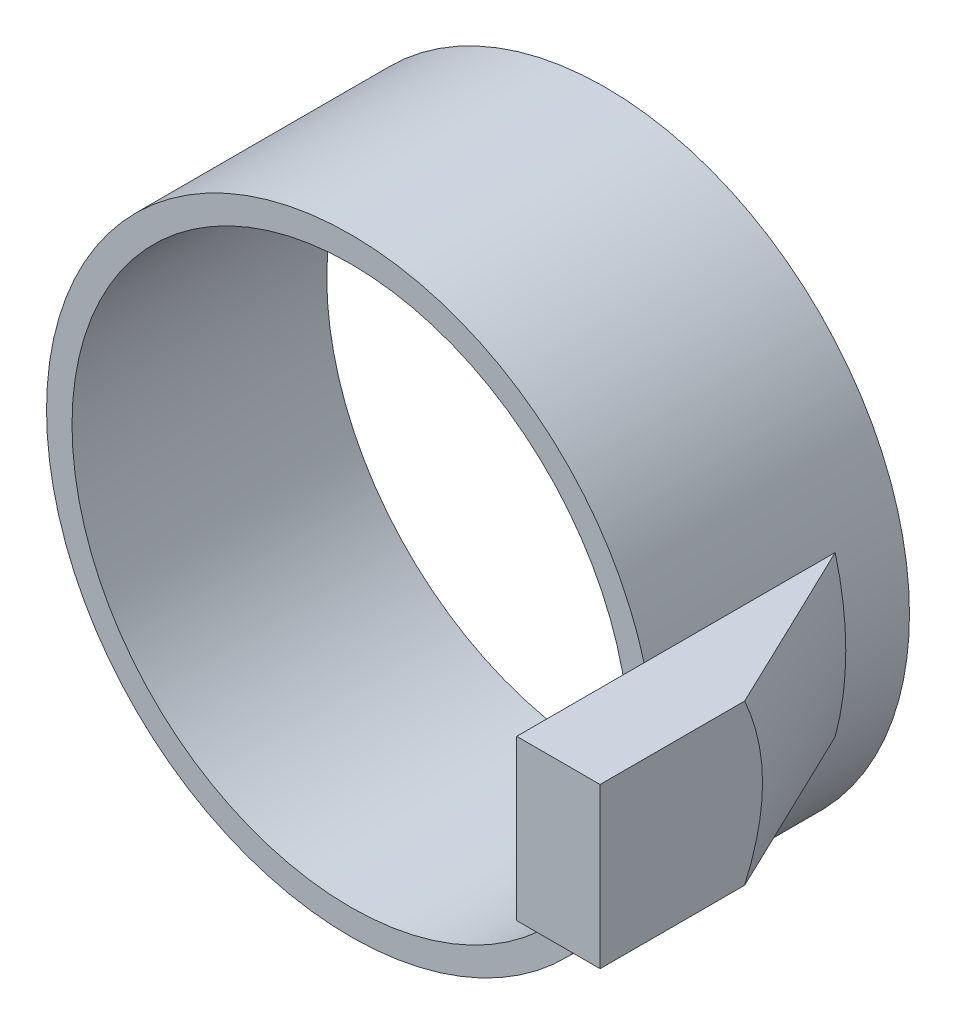
SolidWorks part; units mm, degrees
ref_plane "Front Plane" through (0, 0, 0) normal (1, 0, 0) x (0, 1, 0)
ref_plane "Top Plane" through (0, 0, 0) normal (0, 0, 1) x (0, 1, 0)
ref_plane "Right Plane" through (0, 0, 0) normal (0, 1, 0) x (-1, 0, 0)
sketch "Sketch2" plane through (0, 0, 0) normal (0, 0, 1) x (0, 1, 0)
  circle A0 centre (0, 0) radius 27.7813
  circle A1 centre (0, 0) radius 30.3213
  dimension "D1" = 55.5625
  dimension "D2" = 2.54
extrude "base_ring" add sketch "Sketch2" along normal blind 25.4
sketch "Sketch3" plane through (0, 0, 25.4) normal (0, 0, 1) x (1, 0, 0)
  line L0 (0, 0) -> (30.3213, 0) construction
  line L3 (29.2591, 7.9549) -> (37.5734, 7.9549)
  line L4 (29.2591, 7.9549) -> (29.2591, -7.9549)
  line L5 (29.2591, -7.9549) -> (37.5734, -7.9549)
  line L6 (37.5734, 7.9549) -> (37.5734, -7.9549)
  circle A0 centre (0, 0) radius 30.3213 construction
  point P6 (26.5001, 14.735)
  point P7 (29.2591, 0)
  point P8 (38.166, 5.3156)
  point P13 (37.5734, -7.9549)
  dimension "D1" = 8.3143
extrude "Boss-Extrude3" add sketch "Sketch3" along normal blind 12.7
chamfer "Chamfer1" distance 19.05 angle 25 1 edges at (30.3213, 0, 25.4) first distance on face at (0, 0, 25.4)
